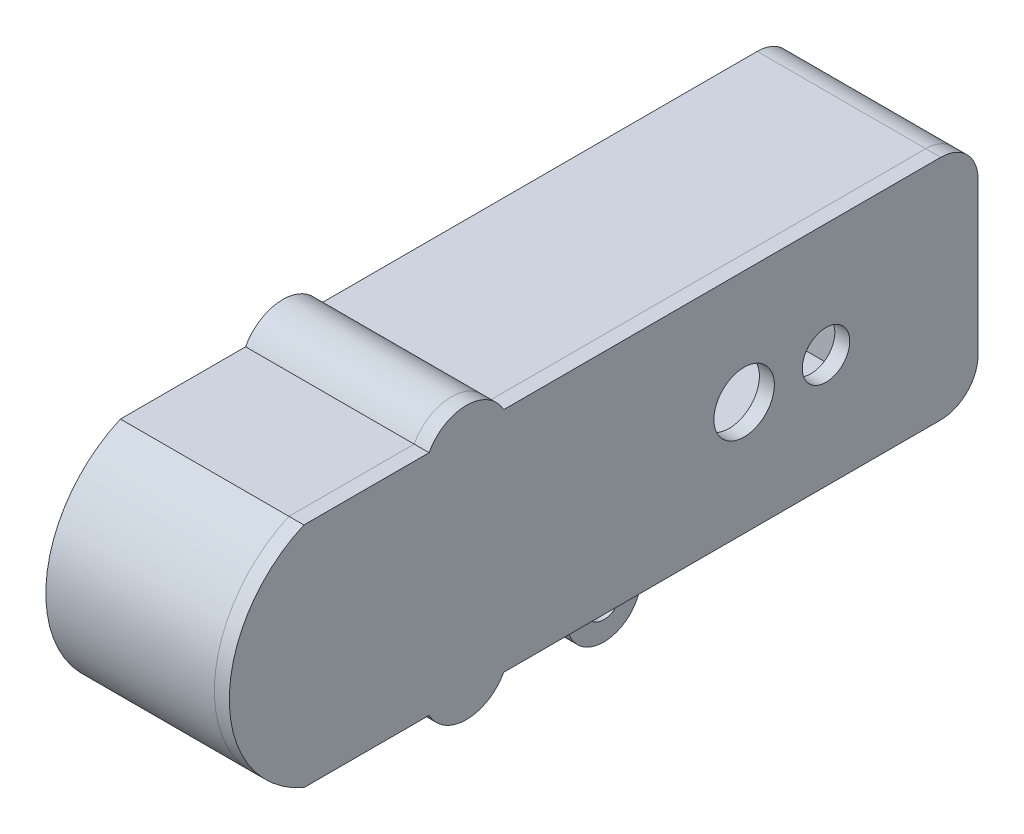
SolidWorks part; units mm, degrees
ref_plane "Front Plane" through (0, 0, 0) normal (0, 0, 1) x (1, 0, 0)
ref_plane "Top Plane" through (0, 0, 0) normal (0, 1, 0) x (1, 0, 0)
ref_plane "Right Plane" through (0, 0, 0) normal (1, 0, 0) x (0, 0, -1)
sketch "Sketch1" plane through (0, 0, 0) normal (1, 0, 0) x (0, 0, -1)
  line L0 (-25.32, -11.25) -> (8.38, -11.25) construction
  line L1 (20.38, -15.25) -> (-70, -15.25)
  line L2 (20.38, -15.25) -> (20.38, 15.25)
  line L3 (20.38, 15.25) -> (-70, 15.25)
  line L4 (-70, -15.25) -> (-70, 15.25) construction
  line L5 (11.38, -8.25) -> (11.38, 8.25) construction
  line L6 (-25.32, -11.25) -> (8.38, -11.25) construction
  line L7 (11.38, -8.25) -> (11.38, 8.25) construction
  line L8 (8.38, 11.25) -> (-25.32, 11.25) construction
  line L9 (8.38, 11.25) -> (-25.32, 11.25) construction
  line L10 (8.38, 15.25) -> (8.38, 11.25) construction
  line L11 (20.38, 8.25) -> (11.38, 8.25) construction
  line L12 (8.38, -11.25) -> (8.38, -15.25) construction
  line L13 (16.38, 2) -> (16.38, -2) construction
  line L14 (16.38, 2) -> (16.38, -2) construction
  line L15 (16.38, 2) -> (20.38, 2) construction
  line L17 (-70, 0) -> (-80, 0) construction
  arc A0 (-70, 15.25) -> (-70, -15.25) centre (-63.3719, 0) ccw
  dimension "D2" = 10
  dimension "D1" = 4
extrude "Boss-Extrude1" add sketch "Sketch1" against normal blind 3
fillet "Fillet1" radius 5 2 edges at (-1.5, -15.25, -20.38) (-1.5, 15.25, -20.38)
sketch "Sketch2" plane through (0, 0, 0) normal (1, 0, 0) x (0, 0, -1)
  line L3 (-69.3438, -12.25) -> (15.38, -12.25)
  line L4 (17.38, -10.25) -> (17.38, 10.25)
  line L5 (15.38, 12.25) -> (-69.3438, 12.25)
  line L11 (-70, -15.25) -> (20.38, -15.25)
  line L12 (20.38, 15.25) -> (-70, 15.25)
  line L13 (20.38, -15.25) -> (20.38, 15.25)
  line L14 (-70, -15.25) -> (15.38, -15.25)
  line L15 (15.38, 15.25) -> (-70, 15.25)
  line L16 (20.38, -10.25) -> (20.38, 10.25)
  arc A3 (15.38, 15.25) -> (20.38, 10.25) centre (15.38, 10.25) cw
  arc A4 (-70, 15.25) -> (-70, -15.25) centre (-63.3719, 0) ccw
  arc A5 (-70, 15.25) -> (-70, -15.25) centre (-63.3719, 0) ccw
  arc A11 (20.38, 10.25) -> (15.38, 15.25) centre (15.38, 10.25) ccw construction
  arc A12 (15.38, -15.25) -> (20.38, -10.25) centre (15.38, -10.25) ccw
  arc A13 (15.38, -15.25) -> (20.38, -10.25) centre (15.38, -10.25) ccw construction
  arc A16 (15.38, -12.25) -> (17.38, -10.25) centre (15.38, -10.25) ccw
  arc A17 (15.38, 12.25) -> (17.38, 10.25) centre (15.38, 10.25) cw
  arc A18 (-69.3438, 12.25) -> (-69.3438, -12.25) centre (-63.3719, 0) ccw
  dimension "D1" = 0
  dimension "D2" = 3
extrude "Boss-Extrude2" add sketch "Sketch2" along normal offset from surface (19.6 mm away) 1 offset beyond the face yes
sketch "Sketch3" plane through (0, 0, 0) normal (1, 0, 0) x (0, 0, -1)
  line L0 (-34.62, 12.25) -> (-34.62, 11.25)
  line L1 (-69.3438, -12.25) -> (15.38, -12.25) construction
  line L2 (-34.62, 11.25) -> (10.38, 11.25)
  line L3 (11.38, 10.25) -> (11.38, -12.25)
  line L5 (11.38, -12.25) -> (15.38, -12.25)
  line L6 (11.38, 8.25) -> (11.38, -8.25) construction
  line L7 (-25.32, 11.25) -> (8.38, 11.25) construction
  line L10 (15.38, 12.25) -> (-34.62, 12.25)
  line L11 (17.38, -10.25) -> (17.38, 10.25)
  line L12 (15.38, 12.25) -> (-69.3438, 12.25) construction
  line L13 (17.38, -10.25) -> (17.38, 10.25) construction
  arc A0 (10.38, 11.25) -> (11.38, 10.25) centre (10.38, 10.25) cw
  arc A1 (17.38, 10.25) -> (15.38, 12.25) centre (15.38, 10.25) ccw construction
  arc A3 (17.38, 10.25) -> (15.38, 12.25) centre (15.38, 10.25) ccw
  arc A4 (15.38, -12.25) -> (17.38, -10.25) centre (15.38, -10.25) ccw
  dimension "D1" = 1
  dimension "D2" = 45
extrude "Boss-Extrude5" add sketch "Sketch3" along normal up to surface (18.6 mm away)
sketch "Sketch5" plane through (18.6, 0, 0) normal (1, 0, 0) x (0, 0, -1)
  line L5 (10.38, -3.5) -> (17.38, -3.5)
  line L6 (10.38, -3.5) -> (10.38, 3.5)
  line L7 (10.38, 3.5) -> (17.38, 3.5)
  line L12 (17.38, -3.5) -> (17.38, 3.5)
  line L13 (10.38, -3.5) -> (17.38, 3.5) construction
  line L14 (10.38, 3.5) -> (17.38, -3.5) construction
  line L15 (17.38, 10.25) -> (17.38, -10.25) construction
  arc A2 (15.18, 0) -> (12.58, 0) centre (13.88, 0) ccw construction
  arc A3 (15.18, 0) -> (12.58, 0) centre (13.88, 0) ccw construction
extrude "Cut-Extrude1" cut sketch "Sketch5" against normal offset from surface (11.8 mm away) 1 offset beyond the face yes
sketch "Sketch6" plane through (0, 0, 0) normal (1, 0, 0) x (0, 0, -1)
  line L0 (-49.019, 14.805) -> (-47.419, 14.805) construction
  line L1 (-49.019, 14.805) -> (-47.419, 14.805) construction
  line L2 (-49.019, -15.055) -> (-47.419, -15.055) construction
  line L3 (-49.019, -15.055) -> (-47.419, -15.055) construction
  line L4 (-49.019, 14.805) -> (-49.019, -15.055) construction
  line L5 (-47.419, -15.055) -> (-47.419, 14.805) construction
  line L6 (-50.019, 15.805) -> (-46.419, 15.805)
  line L7 (-46.419, -16.055) -> (-46.419, 15.805)
  line L8 (-50.019, -16.055) -> (-46.419, -16.055)
  line L9 (-50.019, 15.805) -> (-50.019, -16.055)
  dimension "D1" = 1
extrude "Cut-Extrude2" cut sketch "Sketch6" along normal through all
sketch "Sketch7" plane through (-3, 0, 0) normal (-1, 0, 0) x (0, 0, 1)
  line L2 (-15.38, 15.25) -> (70, 15.25) construction
  line L6 (48.219, 15.25) -> (48.219, 18.25) construction
  line L7 (50.019, 15.25) -> (46.419, 15.25) construction
  line L8 (53.219, 15.25) -> (43.219, 15.25)
  line L9 (0, 0) -> (12.8243, 0) construction
  line L10 (48.219, -15.25) -> (48.219, -18.25) construction
  line L11 (53.219, -15.25) -> (43.219, -15.25)
  arc A0 (53.219, 15.25) -> (43.219, 15.25) centre (48.219, 12.5833) ccw
  arc A1 (53.219, -15.25) -> (43.219, -15.25) centre (48.219, -12.5833) cw
  dimension "D1" = 10
  dimension "D2" = 3
extrude "Boss-Extrude6" add sketch "Sketch7" against normal up to surface (22.6 mm away) up to face at (19.6, 0, 3.8114)
sketch "Sketch8" plane through (19.6, 0, 0) normal (1, 0, 0) x (0, 0, -1)
  line L0 (-53.219, 15.25) -> (-70, 15.25)
  line L1 (-43.219, -15.25) -> (-53.219, -15.25)
  line L3 (-70, -15.25) -> (20.38, -15.25)
  line L4 (20.38, 15.25) -> (-70, 15.25)
  line L5 (20.38, -15.25) -> (20.38, 15.25)
  line L6 (-70, -15.25) -> (-53.219, -15.25)
  line L7 (15.38, 15.25) -> (-43.219, 15.25)
  line L8 (20.38, -10.25) -> (20.38, 10.25)
  line L9 (-53.219, 15.25) -> (-43.219, 15.25)
  line L16 (-43.219, -15.25) -> (15.38, -15.25)
  arc A0 (15.38, -15.25) -> (20.38, -10.25) centre (15.38, -10.25) ccw
  arc A1 (-70, 15.25) -> (-70, -15.25) centre (-63.3719, 0) ccw
  arc A2 (-70, 15.25) -> (-70, -15.25) centre (-63.3719, 0) ccw
  arc A3 (-53.219, -15.25) -> (-43.219, -15.25) centre (-48.219, -12.5833) ccw
  arc A4 (-53.219, -15.25) -> (-43.219, -15.25) centre (-48.219, -12.5833) ccw
  arc A5 (-43.219, 15.25) -> (-53.219, 15.25) centre (-48.219, 12.5833) ccw
  arc A6 (-43.219, 15.25) -> (-53.219, 15.25) centre (-48.219, 12.5833) ccw
  arc A8 (15.38, 15.25) -> (20.38, 10.25) centre (15.38, 10.25) cw
  arc A9 (20.38, 10.25) -> (15.38, 15.25) centre (15.38, 10.25) ccw construction
  arc A21 (15.38, -15.25) -> (20.38, -10.25) centre (15.38, -10.25) ccw construction
  point P24 (-70.3887, 15.0751)
  dimension "D1" = 0
  dimension "D2" = 0
  dimension "D3" = 0
extrude "Boss-Extrude7" add sketch "Sketch8" along normal blind 2 separate body
ref_plane "Plane2" through (9.3, 0, 0) normal (1, 0, 0) x (0, 0, -1)
sketch "Sketch9" plane through (9.3, 0, 0) normal (1, 0, 0) x (0, 0, -1)
  line L0 (-27.5, -15.25) -> (-27.5, -20.75)
  line L2 (-17.5, -20.75) -> (-17.5, -15.25)
  line L3 (-17.5, -15.25) -> (-27.5, -15.25)
  line L4 (-22.5, -25.75) -> (-22.5, -15.25) construction
  line L5 (-22.5, -20.75) -> (-72.5, -20.75) construction
  line L6 (-72.5, -20.75) -> (-72.5, -23) construction
  line L7 (-43.219, -15.25) -> (15.38, -15.25) construction
  arc A0 (-27.5, -20.75) -> (-17.5, -20.75) centre (-22.5, -20.75) ccw
  dimension "D1" = 10
  dimension "D2" = 5.5
  dimension "D3" = 50
extrude "Boss-Extrude8" add sketch "Sketch9" along normal mid plane 10
sketch "Sketch10" [suppressed] plane through (-3, 0, 0) normal (-1, 0, 0) x (0, 0, 1)
  line L0 (72.2754, -39.9249) -> (69.4884, -40.8677)
  line L1 (-6.0881, -39.9249) -> (70, -39.9249) construction
  line L2 (72.2754, -39.9249) -> (70, -39.9249)
  line L3 (0, 0) -> (15.2828, 0) construction
  line L4 (72.2754, 39.9249) -> (69.4884, 40.8677)
  line L5 (72.2754, 39.9249) -> (70, 39.9249)
  line L6 (-4.7, 0) -> (70, -39.9249) construction
  arc A0 (70, 39.9249) -> (70, -39.9249) centre (-4.7, 0) ccw construction
  arc A1 (69.4884, -40.8677) -> (70, -39.9249) centre (-4.7, 0) ccw
  arc A2 (69.4884, 40.8677) -> (70, 39.9249) centre (-4.7, 0) cw
  point P12 (70.8819, -40.3963)
  dimension "D1" = 1
extrude "Cut-Extrude3" [suppressed] cut sketch "Sketch10" against normal through all
sketch "Sketch11" plane through (-3, 0, 0) normal (-1, 0, 0) x (0, 0, 1)
  line L0 (55.019, -4.125) -> (53.0647, -4.125) construction
  line L1 (55.019, 3.875) -> (55.019, -4.125) construction
  line L2 (55.019, 3.875) -> (53.0647, 3.875) construction
  line L3 (47.419, 9.875) -> (49.019, 9.875) construction
  line L4 (49.019, -10.125) -> (47.419, -10.125) construction
  line L5 (41.419, -6.125) -> (44.2041, -6.125) construction
  line L6 (41.419, -6.125) -> (41.419, 5.875) construction
  line L7 (41.419, 5.875) -> (44.2041, 5.875) construction
  line L8 (55.019, -4.125) -> (53.0647, -4.125) construction
  line L9 (55.019, 3.875) -> (55.019, -4.125) construction
  line L10 (55.019, 3.875) -> (53.0647, 3.875) construction
  line L11 (47.419, 9.875) -> (49.019, 9.875) construction
  line L12 (49.019, -10.125) -> (47.419, -10.125) construction
  line L13 (41.419, -6.125) -> (44.2041, -6.125) construction
  line L14 (41.419, -6.125) -> (41.419, 5.875) construction
  line L15 (41.419, 5.875) -> (44.2041, 5.875) construction
  line L16 (47.419, 9.875) -> (47.419, 5.875) construction
  line L17 (47.419, 5.875) -> (44.2041, 5.875) construction
  line L18 (53.0647, 3.875) -> (49.019, 3.875) construction
  line L19 (49.019, 3.875) -> (49.019, 9.875) construction
  line L20 (44.2041, -6.125) -> (47.419, -6.125) construction
  line L21 (47.419, -6.125) -> (47.419, -10.125) construction
  line L22 (49.019, -10.125) -> (49.019, -4.125) construction
  line L23 (49.019, -4.125) -> (53.0647, -4.125) construction
  line L24 (56.019, -5.125) -> (53.0647, -5.125)
  line L25 (50.019, -5.125) -> (53.0647, -5.125)
  line L26 (50.019, -11.125) -> (50.019, -5.125)
  line L27 (50.019, -11.125) -> (46.419, -11.125)
  line L28 (46.419, -7.125) -> (46.419, -11.125)
  line L29 (44.2041, -7.125) -> (46.419, -7.125)
  line L30 (40.419, -7.125) -> (44.2041, -7.125)
  line L31 (40.419, -7.125) -> (40.419, 6.875)
  line L32 (40.419, 6.875) -> (44.2041, 6.875)
  line L33 (46.419, 6.875) -> (44.2041, 6.875)
  line L34 (46.419, 10.875) -> (46.419, 6.875)
  line L35 (46.419, 10.875) -> (50.019, 10.875)
  line L36 (50.019, 4.875) -> (50.019, 10.875)
  line L37 (53.0647, 4.875) -> (50.019, 4.875)
  line L38 (56.019, 4.875) -> (53.0647, 4.875)
  line L39 (56.019, 4.875) -> (56.019, -5.125)
  dimension "D1" = 1
extrude "Cut-Extrude4" cut sketch "Sketch11" against normal up to next (3 mm away)
sketch "Sketch12" plane through (0, 0, 0) normal (1, 0, 0) x (0, 0, -1)
  line L0 (-50.019, 12.25) -> (-69.3438, 12.25) construction
  line L1 (-58.97, 8.5) -> (-58.97, -8.5) construction
  line L2 (-25.62, 12.25) -> (-58.97, 12.25)
  line L3 (-25.62, 12.25) -> (-25.62, -12.25)
  line L4 (-25.62, -12.25) -> (-58.97, -12.25)
  line L5 (-58.97, 12.25) -> (-58.97, -12.25)
  line L7 (-69.3438, -12.25) -> (-50.019, -12.25) construction
  line L11 (-25.62, -10.95) -> (-25.62, 10.95) construction
extrude "Cut-Extrude5" cut sketch "Sketch12" along normal through all and the other way blind 2
sketch "Sketch13" plane through (19.6, 0, 0) normal (-1, 0, 0) x (0, 0, 1)
  line L0 (34.62, 4.575) -> (28.12, 4.575)
  line L1 (28.12, 4.575) -> (28.12, -4.575)
  line L2 (28.12, -4.575) -> (34.62, -4.575)
  line L3 (34.62, -4.575) -> (34.62, 4.575)
  line L4 (32.62, 2.575) -> (30.12, 2.575)
  line L5 (32.62, -2.575) -> (32.62, 2.575)
  line L6 (30.12, -2.575) -> (32.62, -2.575)
  line L7 (30.12, 2.575) -> (30.12, -2.575)
  line L8 (32.62, 2.575) -> (30.12, 2.575) construction
  line L9 (32.62, -2.575) -> (32.62, 2.575) construction
  line L10 (30.12, -2.575) -> (32.62, -2.575) construction
  line L11 (30.12, 2.575) -> (30.12, -2.575) construction
  circle A0 centre (0, 0) radius 2.68 construction
  circle A1 centre (0, 0) radius 2.68 construction
  arc A2 (13.0296, 0) -> (8.9296, 0) centre (10.9796, 0) ccw construction
  arc A3 (13.0296, 0) -> (8.9296, 0) centre (10.9796, 0) ccw construction
  circle A4 centre (0, 0) radius 3.18
  circle A5 centre (10.9796, 0) radius 4.05
  dimension "D3" = 2
  dimension "D1" = 0
  dimension "D2" = 0.5
  dimension "D4" = 2
extrude "Cut-Extrude6" cut sketch "Sketch13" against normal through all
sketch "Sketch14" plane through (21.6, 0, 0) normal (1, 0, 0) x (0, 0, -1)
  line L12 (-34.62, -4.575) -> (-28.12, -4.575)
  line L13 (-28.12, -4.575) -> (-28.12, 4.575)
  line L14 (-28.12, 4.575) -> (-34.62, 4.575)
  line L15 (-34.62, 4.575) -> (-34.62, -4.575)
  line L16 (-34.62, -4.575) -> (-28.12, -4.575)
  line L17 (-28.12, -4.575) -> (-28.12, 4.575)
  line L18 (-28.12, 4.575) -> (-34.62, 4.575)
  line L19 (-34.62, 4.575) -> (-34.62, -4.575)
  dimension "D3" = 0
extrude "Boss-Extrude9" add sketch "Sketch14" against normal offset from surface (1.17 mm away) 0.5
sketch "Sketch15" plane through (0, 0, 0) normal (1, 0, 0) x (0, 0, -1)
  line L2 (-69.3438, 12.25) -> (-58.97, 12.25)
  line L3 (-58.97, 12.25) -> (-58.97, -12.25)
  line L9 (-58.97, 12.25) -> (-58.97, -12.25) construction
  line L11 (-58.97, -12.25) -> (-69.3438, -12.25)
  arc A1 (-69.3438, -12.25) -> (-69.3438, 12.25) centre (-63.3719, 0) cw
  arc A4 (-69.3438, 12.25) -> (-69.3438, -12.25) centre (-63.3719, 0) ccw construction
extrude "Boss-Extrude10" add sketch "Sketch15" along normal up to surface (18.6 mm away) up to face at (18.6, 9.3902, -4.0827)
sketch "Sketch16" [suppressed] plane through (21.6, 0, 0) normal (1, 0, 0) x (0, 0, -1)
  line L0 (-66.0069, 15.25) -> (-66.0069, -15.25) construction
  line L1 (-63.3399, 2.1489) -> (-63.3399, -2.1489)
  line L2 (-63.3399, 0) -> (-62.5819, 0) construction
  line L3 (-63.3399, 0) -> (-69.4319, 0) construction
  line L4 (-69.1819, 0) -> (-69.1819, -0.549) construction
  line L5 (-69.1819, -0.549) -> (-63.3399, -0.549) construction
  circle A0 centre (-66.0069, 0) radius 3.175 construction
  arc A1 (-63.3399, 2.1489) -> (-63.3399, -2.1489) centre (-66.0069, 0) ccw
  circle A2 centre (-66.0069, 0) radius 3.425 construction
  dimension "D1" = 6.35
  dimension "D3" = 5.842
  dimension "D2" = 0.25
extrude "Cut-Extrude7" [suppressed] cut sketch "Sketch16" against normal through all
sketch "Sketch17" [suppressed] plane through (21.6, 0, 0) normal (1, 0, 0) x (0, 0, -1)
  circle A0 centre (-66.0069, 0) radius 3.425
  arc A1 (-63.3399, 2.1489) -> (-63.3399, -2.1489) centre (-66.0069, 0) ccw construction
extrude "Cut-Extrude8" [suppressed] cut sketch "Sketch17" against normal up to surface (2 mm away) up to face at (21.6, 0, 3.18)
hole_wizard "M4 Clearance Hole1" positions "Sketch18" profile "Sketch19" hole size "M4" standard "ANSI Metric" end condition through all
sketch "Sketch18" plane through (14.3, 0, 0) normal (1, 0, 0) x (0, 0, -1)
  arc A0 (-27.5, -20.75) -> (-17.5, -20.75) centre (-22.5, -20.75) ccw construction
  point P0 (-22.5, -20.75)
sketch "Sketch19" plane through (14.3, -20.75, 22.5) normal (0, 1, 0) x (0, 0, -1)
  line L0 (0, 0) -> (0, 17.3)
  line L1 (0, 17.3) -> (2.4, 17.3)
  line L2 (2.4, 17.3) -> (2.4, 0)
  line L5 (2.4, 0) -> (0, 0)
  line L11 (0, -6.35) -> (0, 107.95) construction
  dimension "Thru Hole Dia." = 4.8
  dimension "Thru Hole Depth" = 17.3
sketch "Sketch20" plane through (9.3, 0, 0) normal (1, 0, 0) x (0, 0, -1)
  line L3 (-27.5, -15.25) -> (-27.5, -20.75)
  line L4 (-17.5, -20.75) -> (-17.5, -15.25)
  line L5 (-17.5, -15.25) -> (-27.5, -15.25)
  line L6 (-27.5, -15.25) -> (-27.5, -20.75)
  line L7 (-17.5, -20.75) -> (-17.5, -15.25)
  line L8 (-17.5, -15.25) -> (-27.5, -15.25)
  arc A1 (-27.5, -20.75) -> (-17.5, -20.75) centre (-22.5, -20.75) ccw
  arc A2 (-27.5, -20.75) -> (-17.5, -20.75) centre (-22.5, -20.75) ccw
  dimension "D1" = 0
extrude "Cut-Extrude9" cut sketch "Sketch20" against normal mid plane 0.762
